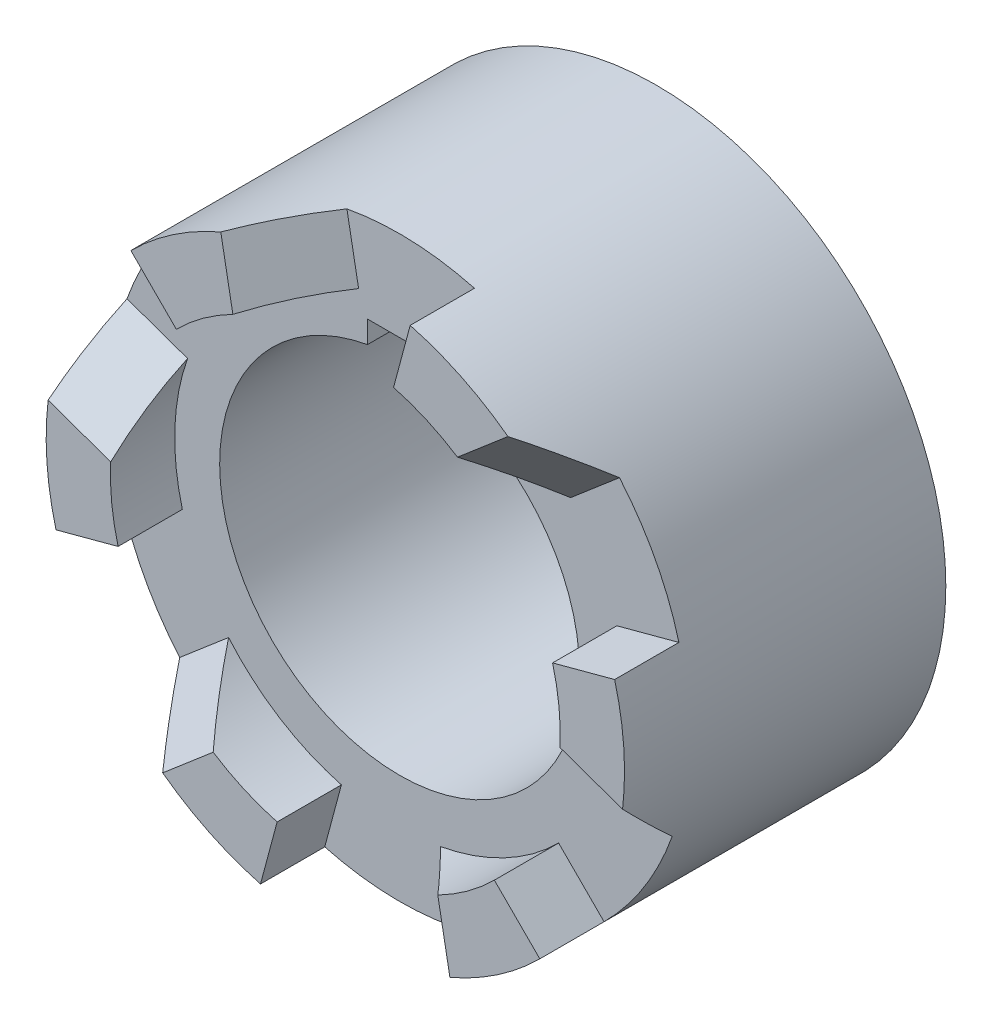
SolidWorks part; units mm, degrees
material "201 Annealed Stainless Steel (SS)"
ref_plane "Front" through (0, 0, 0) normal (0, 0, 1) x (1, 0, 0)
ref_plane "Top" through (0, 0, 0) normal (0, 1, 0) x (1, 0, 0)
ref_plane "Right" through (0, 0, 0) normal (1, 0, 0) x (0, 0, -1)
sketch "Sketch1" plane through (0, 0, 0) normal (0, 0, 1) x (1, 0, 0)
  line L1 (2.5, 15.5) -> (-2.5, 15.5)
  line L2 (2.5, 15.5) -> (2.5, 13.775)
  line L4 (-2.5, 15.5) -> (-2.5, 13.775)
  circle A0 centre (0, 0) radius 22.5
  arc A1 (-2.5, 13.775) -> (2.5, 13.775) centre (0, 0) ccw
  point P8 (0, 15.5)
  dimension "D1" = 45
  dimension "D2" = 28
  dimension "D4" = 1.5
  dimension "D3" = 5
extrude "Boss-Extrude1" add sketch "Sketch1" along normal blind 20
sketch "Sketch2" plane through (0, 0, 20) normal (0, 0, 1) x (1, 0, 0)
  line L1 (-3.1891, 17.207) -> (-4.1003, 22.1232)
  line L2 (0, 0) -> (0, 15.5) construction
  line L3 (0, 0) -> (-11.25, 19.4856) construction
  line L4 (-12.3744, 12.3744) -> (-15.9099, 15.9099)
  line L9 (2.5, 15.5) -> (-2.5, 15.5) construction
  circle A0 centre (0, 0) radius 22.5 construction
  arc A1 (-4.1003, 22.1232) -> (-15.9099, 15.9099) centre (0, 0) ccw
  arc A3 (-3.1891, 17.207) -> (-12.3744, 12.3744) centre (0, 0) ccw
  dimension "D3" = 5
  dimension "D4" = 30
  dimension "D5" = 15
  dimension "D7" = 5
  dimension "D12" = 5
  dimension "D15" = 10.5
extrude "Boss-Extrude2" add sketch "Sketch2" along normal blind 5
chamfer "Chamfer2" distance 5 angle 45 1 edges at (-3.6447, 19.6651, 25)
pattern_circular "CirPattern1" count 6 every 60 about axis through (0, 0, 20) along (0, 0, 1) of "Chamfer2", "Boss-Extrude2"
hole_wizard "M4 Tapped Hole1" positions "3DSketch1" profile "Sketch4" tap size "M4" standard "ISO"
sketch3d "3DSketch1"
  circle A0 centre (0, 0, 0) radius 22.5 construction
  point P0 (0, 19, 0)
  point P7 (0, 0, 22.5)
  dimension "D1" = 3.5
sketch "Sketch4" plane through (0, 19, 0) normal (1, 0, 0) x (0, 1, 0)
  line L0 (0, 0) -> (0, 12.4914)
  line L1 (0, 12.4914) -> (1.65, 11.5)
  line L2 (1.65, 11.5) -> (1.65, 0)
  line L5 (1.65, 0) -> (0, 0)
  line L10 (0, 12.4914) -> (-1.65, 11.5) construction
  line L11 (0, -6.35) -> (0, 107.95) construction
  dimension "Tap Drill Dia." = 3.3
  dimension "Tap Drill Depth" = 11.5
  dimension "Drill Angle" = 118
cosmetic thread "Hole Thread1" parameters "D1"=8, "D2"=4
pattern_circular "CirPattern2" count 4 every 90 about axis through (0, 0, 0) along (0, 0, 1) of "M4 Tapped Hole1"
